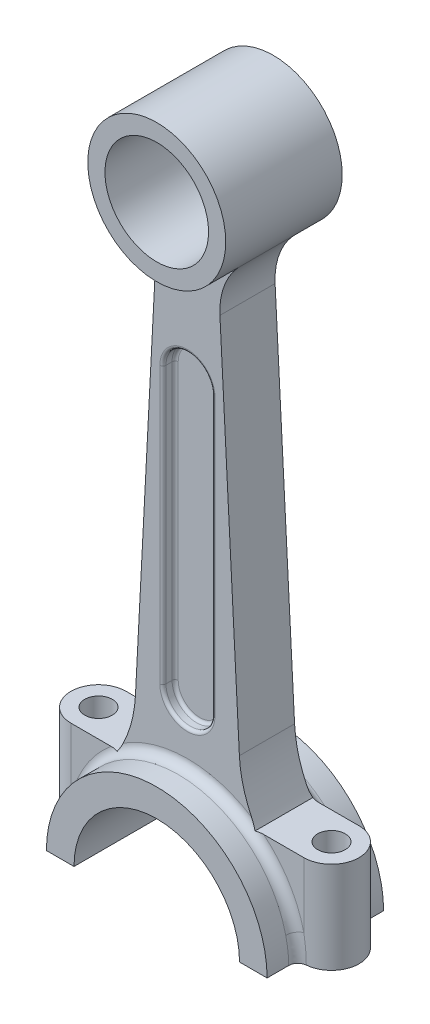
SolidWorks part; units mm, degrees
ref_plane "Front Plane" through (0, 0, 0) normal (0, 0, 1) x (1, 0, 0)
ref_plane "Top Plane" through (0, 0, 0) normal (0, 1, 0) x (1, 0, 0)
ref_plane "Right Plane" through (0, 0, 0) normal (1, 0, 0) x (0, 0, -1)
sketch "Sketch1" plane through (0, 0, 0) normal (0, 0, 1) x (1, 0, 0)
  line L0 (0, 0) -> (0, -201.2) construction
  line L1 (-10, -20.1556) -> (-17.8497, -169.9368)
  line L2 (10, -20.1556) -> (17.8497, -169.9368)
  line L3 (-36, -201.2) -> (-27, -201.2)
  line L4 (27, -201.2) -> (36, -201.2)
  circle A0 centre (0, 0) radius 22.5
  circle A1 centre (0, 0) radius 16.9
  arc A2 (27, -201.2) -> (-27, -201.2) centre (0, -201.2) ccw
  arc A3 (36, -201.2) -> (-36, -201.2) centre (0, -201.2) ccw
  dimension "D1" = 33.8
  dimension "D2" = 45
  dimension "D3" = 54
  dimension "D4" = 72
  dimension "D5" = 201.2
  dimension "D6" = 20
  dimension "D7" = 6
extrude "Boss-Extrude1" add sketch "Sketch1" along normal mid plane 38 contours A1 A0 | A3 A2 | A3 L3 A2 L4 region at (-11.5231, 18.5805, 0) region at (0, -166.005, 0)
extrude "Boss-Extrude2" add sketch "Sketch1<3>" along normal mid plane 18 contours A0 L0 A3 L2 | L0 A0 L1 A3 region at (7.1843, -100.8455, 0) region at (-7.1843, -100.8455, 0)
sketch "Sketch1<3>" plane through (0, 0, 0) normal (0, 0, 1) x (1, 0, 0) same geometry as "Sketch1"
sketch "Sketch2" plane through (0, 0, 9) normal (0, 0, 1) x (1, 0, 0)
  line L0 (0, 0) -> (0, -201.2) construction
  line L1 (0, -145.6) -> (0, -55.6) construction
  line L2 (-8, -145.6) -> (-8, -55.6)
  line L3 (8, -145.6) -> (8, -55.6)
  arc A0 (-8, -145.6) -> (8, -145.6) centre (0, -145.6) ccw
  arc A1 (8, -55.6) -> (-8, -55.6) centre (0, -55.6) ccw
  point P6 (0, -100.6)
  dimension "D2" = 8
  dimension "D1" = 90
extrude "Cut-Extrude1" cut sketch "Sketch2" against normal blind 4
mirror "Mirror1" about plane through (0, 0, 0) normal (0, 0, 1) of "Cut-Extrude1"
fillet "Fillet1" radius 1 16 edges at (0, -153.6, 9) (-8, -100.6, 9) (0, -47.6, 9) (0, -47.6, -9) (8, -100.6, -9) (0, -153.6, -9) (-8, -100.6, 5) (0, -47.6, 5) (8, -100.6, 5) (0, -153.6, 5) (8, -100.6, -5) (0, -47.6, -5) (-8, -100.6, -5) (0, -153.6, -5) (8, -100.6, 9) (-8, -100.6, -9)
fillet "Fillet2" radius 40 2 edges at (17.8497, -169.9368, 0) (-17.8497, -169.9368, 0)
fillet "Fillet3" radius 22.5 2 edges at (10, -20.1556, 0) (-10, -20.1556, 0)
ref_plane "Plane1" through (0, -171.2, 0) normal (0, -1, 0) x (-1, 0, 0)
sketch "Sketch3" plane through (0, -171.2, 0) normal (0, -1, 0) x (-1, 0, 0)
  line L0 (38, 0) -> (-38, 0) construction
  line L1 (38, -9) -> (-38, -9)
  line L2 (38, 9) -> (-38, 9)
  arc A0 (38, -9) -> (38, 9) centre (38, 0) ccw
  arc A1 (-38, 9) -> (-38, -9) centre (-38, 0) ccw
  point P2 (0, 0)
  dimension "D2" = 9
  dimension "D1" = 76
extrude "Boss-Extrude3" add sketch "Sketch3" along normal up to surface (30 mm away) up to face at (-31.5, -201.2, 0)
sketch "Sketch4" plane through (0, 0, 9) normal (0, 0, 1) x (1, 0, 0)
  line L1 (-27, -201.2) -> (27, -201.2)
  line L2 (-27, -201.2) -> (27, -201.2)
  arc A1 (27, -201.2) -> (-27, -201.2) centre (0, -201.2) ccw
  arc A2 (27, -201.2) -> (-27, -201.2) centre (0, -201.2) ccw
  dimension "D1" = 0
extrude "Cut-Extrude2" cut sketch "Sketch4" against normal through all
sketch "Sketch5" plane through (0, -171.2, 0) normal (0, 1, 0) x (1, 0, 0)
  circle A0 centre (-38, 0) radius 4.5
  circle A1 centre (38, 0) radius 4.5
  dimension "D1" = 9
  dimension "D2" = 9
extrude "Cut-Extrude3" cut sketch "Sketch5" against normal through all
fillet "Fillet4" radius 3 2 edges at (0, -165.2, -9) (0, -165.2, 9)
